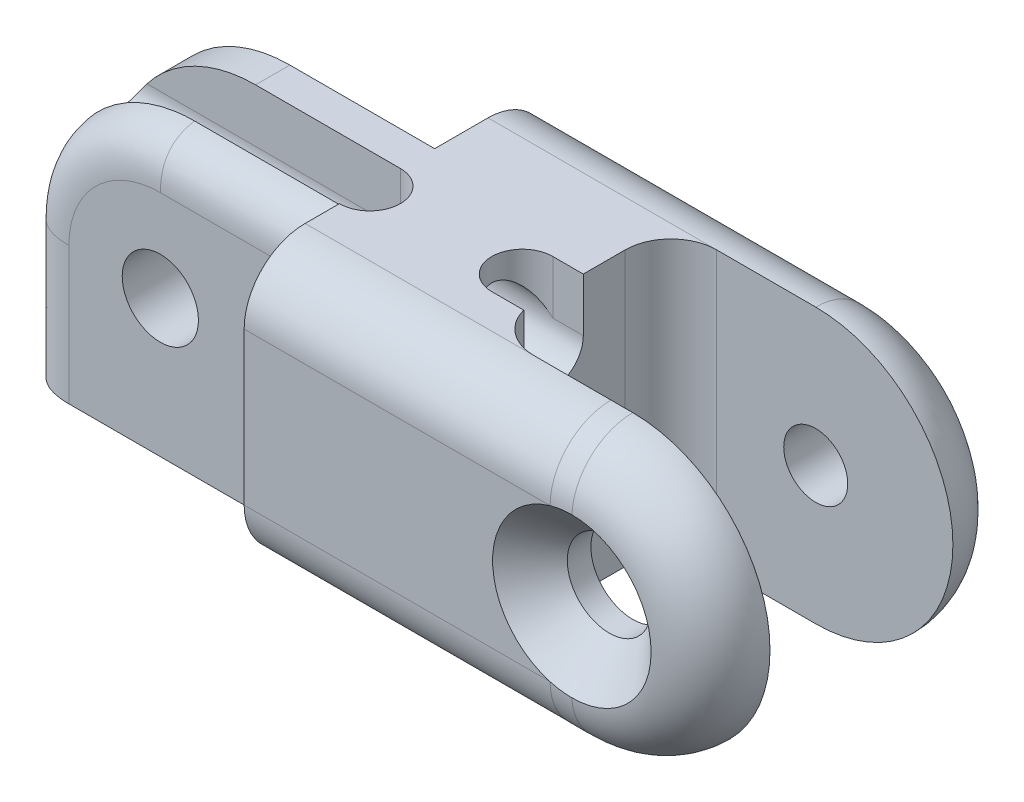
SolidWorks part; units mm, degrees
ref_plane "Front Plane" through (0, 0, 0) normal (0, 0, 1) x (1, 0, 0)
ref_plane "Top Plane" through (0, 0, 0) normal (0, 1, 0) x (1, 0, 0)
ref_plane "Right Plane" through (0, 0, 0) normal (1, 0, 0) x (0, 0, -1)
sketch "Sketch2" plane through (0, 0, 0) normal (0, 1, 0) x (1, 0, 0)
  line L0 (-6, 10) -> (24.5, 10)
  line L1 (24.5, 10) -> (24.5, 6)
  line L2 (24.5, 6) -> (9, 6)
  line L3 (6, 3) -> (6, -3)
  line L4 (9, -6) -> (24.5, -6)
  line L5 (24.5, -6) -> (24.5, -10)
  line L7 (-24.5, -6) -> (-24.5, 2.5)
  line L8 (-49.3622, 0) -> (56.3776, 0) construction
  line L9 (0, 21.2372) -> (0, -19.0689) construction
  line L10 (6, 3) -> (9, 3) construction
  line L11 (9, 3) -> (9, 6) construction
  line L16 (-6, -10) -> (24.5, -10)
  line L18 (-24.5, -6) -> (-6, -6)
  line L19 (-6, -6) -> (-6, -10)
  line L20 (-24.5, 2.5) -> (-6, 2.5)
  line L21 (-6, 2.5) -> (-6, 10)
  arc A0 (9, 6) -> (6, 3) centre (9, 3) ccw
  arc A1 (9, -6) -> (6, -3) centre (9, -3) cw
  point P13 (9, 3)
  dimension "D1" = 49
  dimension "D2" = 20
  dimension "D3" = 4
  dimension "D4" = 18.5
  dimension "D5" = 12
  dimension "D6" = 3
  dimension "D7" = 3
  dimension "D8" = 7.5
  dimension "D9" = 4
  dimension "D10" = 8.5
  dimension "D11" = 18.5
extrude "Boss-Extrude1" add sketch "Sketch2" along normal blind 18
sketch "Sketch5" plane through (0, 0, 10) normal (0, 0, 1) x (1, 0, 0)
  line L0 (-24.5, 9) -> (31.8491, 9) construction
  line L1 (-15.5, 18) -> (-15.5, 0) construction
  line L2 (24.5, 18) -> (24.5, 0) construction
  line L3 (-6, 18) -> (24.5, 18) construction
  line L4 (15.5, 18) -> (15.5, 0) construction
  line L5 (-24.5, 18) -> (-24.5, 0) construction
  line L6 (-24.5, 9) -> (-24.5, 0)
  line L7 (-24.5, 18) -> (-6, 18) construction
  line L8 (-24.5, 0) -> (15.5, 0)
  line L9 (-15.5, 18) -> (15.5, 18)
  arc A0 (-15.5, 18) -> (-24.5, 9) centre (-15.5, 9) ccw
  arc A1 (15.5, 0) -> (15.5, 18) centre (15.5, 9) ccw
  circle A2 centre (-15.5, 9) radius 2.5
  dimension "D2" = 5
  dimension "D1" = 9
extrude "Cut-Extrude1" cut sketch "Sketch5" against normal blind 20 flip side to cut
sketch "Sketch6" plane through (0, 0, 10) normal (0, 0, 1) x (1, 0, 0)
  line L0 (15.5, 0) -> (15.5, 18) construction
  point P4 (15.5, 9)
hole_wizard "CSK for M5 Countersunk Flat Head Screw1" positions "Sketch7" profile "Sketch8" countersink size "M5" standard "DIN" end condition up to next
sketch "Sketch7" plane through (0, 0, 10) normal (0, 0, 1) x (1, 0, 0)
  point P0 (15.5, 9)
sketch "Sketch8" plane through (15.5, 9, 10) normal (1, 0, 0) x (0, -1, 0)
  line L0 (0, 0) -> (0, 4)
  line L1 (0, 4) -> (2.75, 4)
  line L2 (2.75, 4) -> (2.75, 2.45)
  line L3 (2.75, 2.45) -> (5.2, 0)
  line L5 (5.2, 0) -> (0, 0)
  line L6 (-2.75, 2.45) -> (-5.2, 0) construction
  line L11 (0, -6.35) -> (0, 107.95) construction
  dimension "Thru Hole Dia." = 5.5
  dimension "Thru Hole Depth" = 4
  dimension "Near C'Sink Dia." = 10.4
  dimension "Near C'Sink Angle" = 90
hole_wizard "M5 Tapped Hole1" positions "Sketch9" profile "Sketch11" tap size "M5" standard "DIN" end condition through all
sketch "Sketch9" plane through (0, 0, 10) normal (0, 0, 1) x (1, 0, 0)
  point P0 (15.5, 9)
sketch "Sketch11" plane through (15.5, 9, 10) normal (1, 0, 0) x (0, -1, 0)
  line L0 (0, 0) -> (0, 20)
  line L1 (0, 20) -> (2.1, 20)
  line L2 (2.1, 20) -> (2.1, 3.1)
  line L3 (2.1, 3.1) -> (5.2, 0)
  line L5 (5.2, 0) -> (0, 0)
  line L6 (-2.1, 3.1) -> (-5.2, 0) construction
  line L11 (0, -6.35) -> (0, 107.95) construction
  dimension "Thru Tap Drill Dia." = 4.2
  dimension "Thru Tap Drill Depth" = 20
  dimension "Near C'Sink Dia." = 10.4
  dimension "Near C'Sink Angle" = 90
cosmetic thread "Hole Thread1" parameters "D2"=5
fillet "Fillet1" radius 4 2 edges at (4.75, 0, 10) (4.75, 18, 10)
fillet "Fillet2" radius 4 3 edges at (4.75, 0, -10) (24.5, 9, -10) (4.75, 18, -10)
fillet "Fillet3" radius 3 3 edges at (-24.5, 4.5, 6) (-10.75, 18, 6) (-21.864, 15.364, 6) conic rho 0.5
sketch "Sketch12" plane through (6, 0, 0) normal (1, 0, 0) x (0, 0, -1)
  line L0 (-1.75, -3.7946) -> (-1.75, 21.9566) construction
  line L1 (-3, 18) -> (3, 18) construction
  circle A0 centre (-1.75, 14.5) radius 2
  dimension "D1" = 4
  dimension "D2" = 3.5
  dimension "D3" = 1.75
extrude "Cut-Extrude2" cut sketch "Sketch12" against normal through all both and the other way through all
sketch "Sketch13" plane through (0, 18, 0) normal (0, 1, 0) x (1, 0, 0)
  line L0 (-24, 0.25) -> (-6, 0.25)
  line L3 (-24, -3.75) -> (-24, 0.25)
  line L4 (-24, -3.75) -> (-6, -3.75)
  line L5 (-6, -3) -> (-6, -6) construction
  line L6 (6, 0) -> (-35.9451, 0) construction
  line L7 (6, -3) -> (6, 3) construction
  arc A0 (-6, -3.75) -> (-6, 0.25) centre (-6, -1.75) ccw
  dimension "D2" = 4
  dimension "D4" = 0
  dimension "D1" = 4
  dimension "D3" = 18
  dimension "D5" = 0.25
extrude "Cut-Extrude3" cut sketch "Sketch13" against normal blind 3.5
sketch "Sketch15" plane through (0, 18, 0) normal (0, 1, 0) x (1, 0, 0)
  line L0 (-0.494, -1.75) -> (8.4177, -1.75) construction
  line L1 (6, -3) -> (6, 3) construction
  line L2 (4, 0.25) -> (9, 0.25)
  line L3 (4, -3.75) -> (9, -3.75)
  line L4 (9, 0.25) -> (9, -3.75)
  arc A0 (4, 0.25) -> (4, -3.75) centre (4, -1.75) ccw
  point P4 (6, 0)
  dimension "D2" = 4
  dimension "D1" = 1.75
  dimension "D3" = 2
  dimension "D4" = 5
extrude "Cut-Extrude4" cut sketch "Sketch15" against normal blind 3.5
sketch "Sketch16" plane through (0, 0, -0.25) normal (0, 0, 1) x (1, 0, 0)
